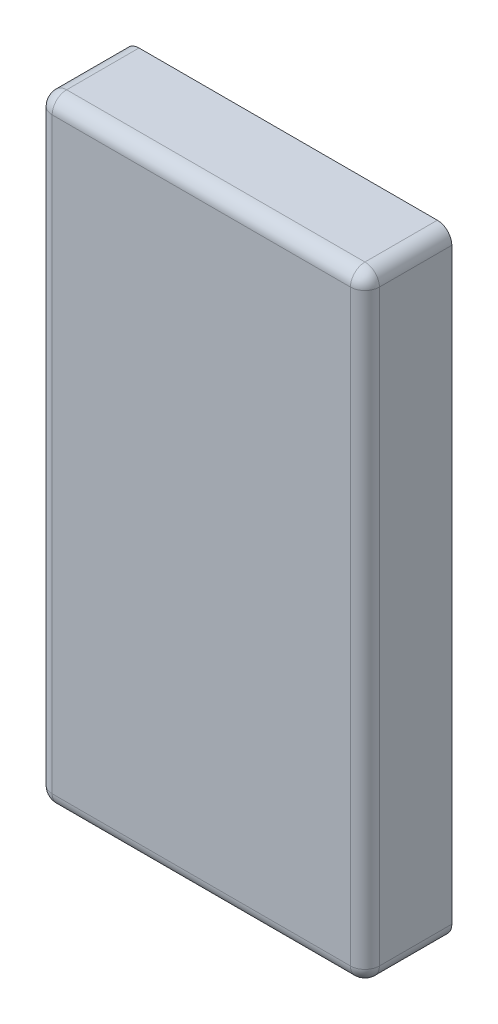
SolidWorks part; units mm, degrees
ref_plane "Plano frontal" through (0, 0, 0) normal (0, 0, 1) x (1, 0, 0)
ref_plane "Plano superior" through (0, 0, 0) normal (0, 1, 0) x (1, 0, 0)
ref_plane "Plano direito" through (0, 0, 0) normal (1, 0, 0) x (0, 0, -1)
sketch "Esboço1" plane through (0, 0, 0) normal (0, 0, 1) x (1, 0, 0)
  line L1 (-11.3, -21.3) -> (11.3, -21.3)
  line L2 (-11.3, -21.3) -> (-11.3, 21.3)
  line L3 (-11.3, 21.3) -> (11.3, 21.3)
  line L4 (11.3, -21.3) -> (11.3, 21.3)
  line L5 (-11.3, -21.3) -> (11.3, 21.3) construction
  line L6 (-11.3, 21.3) -> (11.3, -21.3) construction
  point P0 (0, 0)
  dimension "D1" = 22.6
  dimension "D2" = 42.6
extrude "Ressalto-extrusão1" add sketch "Esboço1" along normal blind 6
sketch "Esboço2" plane through (0, 0, 0) normal (0, 0, -1) x (-1, 0, 0)
  line L1 (-2.125, -2.125) -> (2.125, -2.125)
  line L2 (-2.125, -2.125) -> (-2.125, 2.125)
  line L3 (-2.125, 2.125) -> (2.125, 2.125)
  line L4 (2.125, -2.125) -> (2.125, 2.125)
  line L5 (-2.125, -2.125) -> (2.125, 2.125) construction
  line L6 (-2.125, 2.125) -> (2.125, -2.125) construction
  line L7 (-4.125, -4.125) -> (4.125, -4.125)
  line L8 (-4.125, -4.125) -> (-4.125, 4.125)
  line L9 (-4.125, 4.125) -> (4.125, 4.125)
  line L10 (4.125, -4.125) -> (4.125, 4.125)
  line L11 (-4.125, -4.125) -> (4.125, 4.125) construction
  line L12 (-4.125, 4.125) -> (4.125, -4.125) construction
  point P0 (0, 0)
  point P6 (0, 0)
  dimension "D1" = 4.25
  dimension "D2" = 4.25
  dimension "D3" = 2
  dimension "D4" = 2
extrude "Ressalto-extrusão2" add sketch "Esboço2" along normal blind 3
fillet "Filete1" radius 1 8 edges at (0, -21.3, 6) (-11.3, 0, 6) (0, 21.3, 6) (11.3, 0, 6) (11.3, 21.3, 3) (-11.3, 21.3, 3) (11.3, -21.3, 3) (-11.3, -21.3, 3)
fillet "Filete2" radius 1 4 edges at (-4.125, 4.125, -1.5) (-4.125, -4.125, -1.5) (4.125, -4.125, -1.5) (4.125, 4.125, -1.5)
sketch "Esboço3" plane through (0, 0, 0) normal (0, 0, -1) x (-1, 0, 0)
  line L0 (-11.3, 0) -> (11.3, 0) construction
  line L1 (-11.3, -20.3) -> (-11.3, 20.3) construction
  line L2 (11.3, 20.3) -> (11.3, -20.3) construction
  circle A0 centre (0, 15) radius 2.5
  circle A1 centre (0, -15) radius 2.5
  dimension "D1" = 5
  dimension "D2" = 15
extrude "Corte-extrusão1" cut sketch "Esboço3" against normal blind 3
